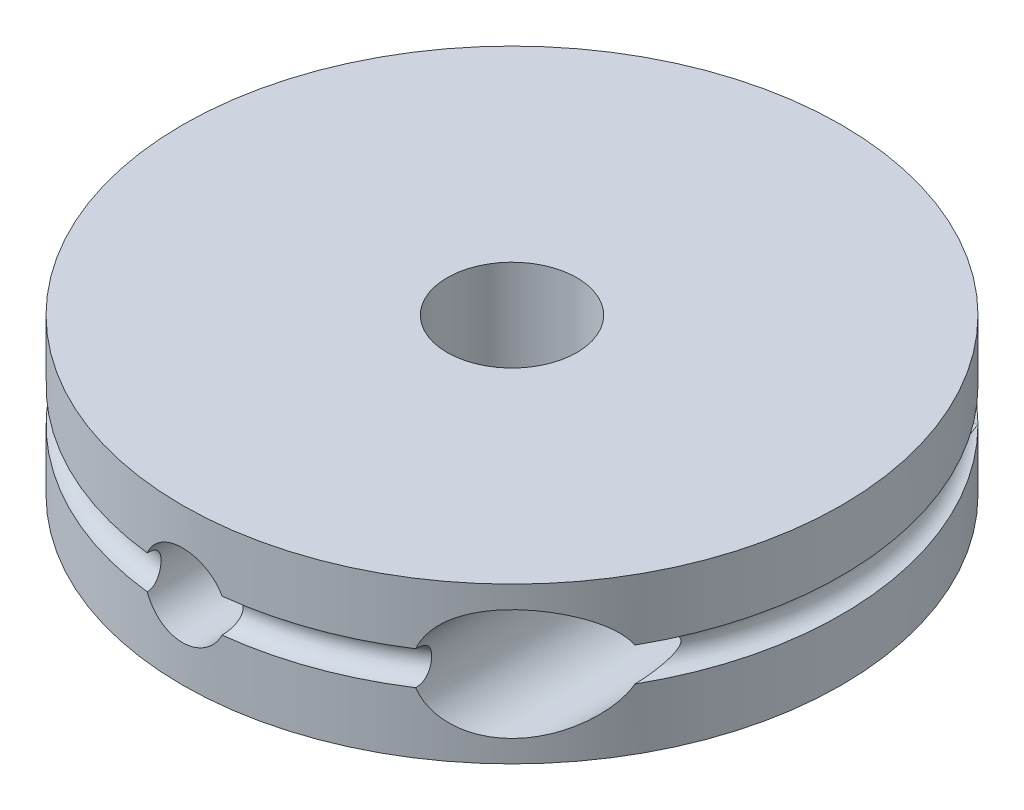
SolidWorks part; units mm, degrees
material "6063-T5"
ref_plane "Front Plane" through (0, 0, 0) normal (0, 0, 1) x (1, 0, 0)
ref_plane "Top Plane" through (0, 0, 0) normal (0, 1, 0) x (1, 0, 0)
ref_plane "Right Plane" through (0, 0, 0) normal (1, 0, 0) x (0, 0, -1)
sketch "BASE" plane through (0, 0, 0) normal (0, 1, 0) x (1, 0, 0)
  circle A0 centre (0, 0) radius 12.7
  circle A1 centre (0, 0) radius 2.5
  dimension "D1" = 25.4
  dimension "D2" = 5
extrude "MAIN_BODY" add sketch "BASE" along normal blind 6
sketch "Sketch4" plane through (0, 0, 0) normal (0, 0, 1) x (1, 0, 0)
  line L0 (12.7, 0) -> (12.7, 6) construction
  line L1 (0, 0) -> (0, 6) construction
  line L2 (-12.7, 0) -> (12.7, 0) construction
  line L3 (12.7, 6) -> (-12.7, 6) construction
  circle A0 centre (12.7, 3) radius 0.65
  dimension "D1" = 1.3
revolve "CABLE_GUIDE" cut sketch "Sketch4" angle 360 about L1
sketch "Sketch5" plane through (0, 0, 0) normal (0, 0, 1) x (1, 0, 0)
  line L0 (0, 3) -> (0, 0) construction
  circle A0 centre (0, 3) radius 1.5811
  dimension "D2" = 3.1623
  dimension "D1" = 3
extrude "Cut-Extrude2" cut sketch "Sketch5" along normal up to next
sketch "Sketch8" plane through (0, 0, 0) normal (0, 0, 1) x (1, 0, 0)
  line L0 (0, 3) -> (12.05, 3) construction
  arc A0 (12.7, 3.65) -> (12.7, 2.35) centre (12.7, 3) ccw construction
  circle A1 centre (8.9803, 3) radius 0.65
  dimension "D1" = 1.3
  dimension "D2" = 8.9803
extrude "Cut-Extrude3" cut sketch "Sketch8" against normal through all both and the other way through all
sketch "Sketch9" plane through (0, 0, 0) normal (0, 0, 1) x (1, 0, 0)
  circle A0 centre (8.9803, 3) radius 2.15
  dimension "D1" = 4.3
extrude "Cut-Extrude4" cut sketch "Sketch9" along normal through all
